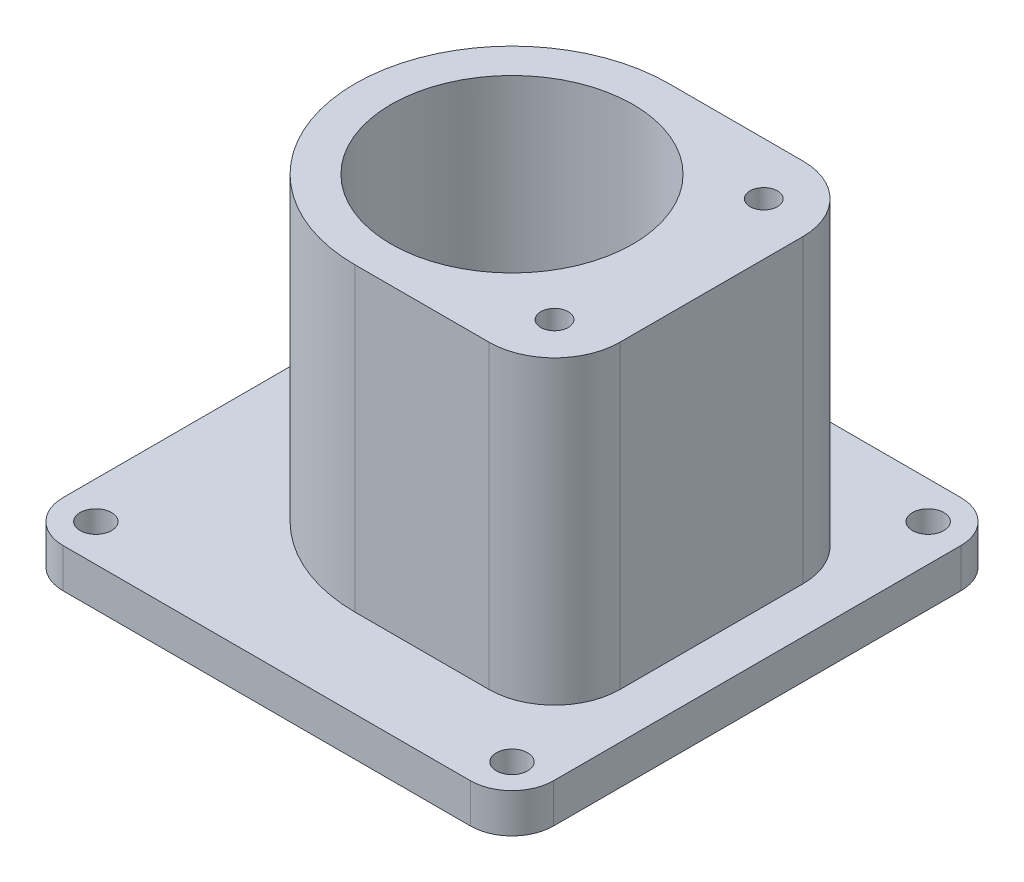
SolidWorks part; units mm, degrees
note: '?' marks a value the reader was unsure of.
ref_plane "Front Plane" through (0, 0, 0) normal (0, 0, 1) x (1, 0, 0)
ref_plane "Top Plane" through (0, 0, 0) normal (0, 1, 0) x (1, 0, 0)
ref_plane "Right Plane" through (0, 0, 0) normal (1, 0, 0) x (0, 0, -1)
ref_axis "X" through (88.99, 0, 0) along (-1, 0, 0)?
ref_axis "Y" through (0, 55, 0) along (0, -1, 0)?
ref_axis "Z" through (0, 0, -88.99) along (0, 0, 1)?
sketch "Sketch1" plane through (0, 0, 0) normal (0, 0, 1) x (1, 0, 0)
  line L0 (0, 0) -> (0, 52.8087) construction
  line L1 (-16.5, 0) -> (-34, 0)
  line L2 (-34, 0) -> (-34, 6)
  line L3 (-34, 6) -> (-24, 6)
  line L4 (-24, 6) -> (-24, 25)
  line L14 (-24, 25) -> (-18.5, 25)
  line L15 (-18.5, 25) -> (-18.5, 13)
  line L21 (-18.5, 13) -> (-16.5, 13)
  line L24 (-16.5, 13) -> (-16.5, 0)
  point P3 (0, 0)
  point P9 (0, 0)
  dimension "D2" = 25
  dimension "D3" = 12
  dimension "D4" = 48
  dimension "D5" = 10
  dimension "D6" = 6
  dimension "D7" = 18.5
  dimension "D10" = 33
revolve "Revolve1" add sketch "Sketch1" angle 360 about L0
sketch "Sketch2" plane through (0, 6, 0) normal (0, 1, 0) x (1, 0, 0)
  line L1 (37.5, -37.5) -> (-37.5, -37.5)
  line L2 (37.5, -37.5) -> (37.5, 37.5)
  line L3 (37.5, 37.5) -> (-37.5, 37.5)
  line L4 (-37.5, -37.5) -> (-37.5, 37.5)
  line L5 (37.5, -37.5) -> (-37.5, 37.5) construction
  line L6 (37.5, 37.5) -> (-37.5, -37.5) construction
  circle A0 centre (0, 0) radius 21
  point P0 (0, 0)
  point P7 (-3.2396, 8.1426)
  dimension "D1" = 75
extrude "Boss-Extrude1" add sketch "Sketch2" against normal up to surface (6 mm away) up to face at (0, 0, -16.5)
hole_wizard "M4 Clearance Hole1" positions "Sketch3" profile "Sketch4" hole size "M4" standard "DIN" end condition up to next
sketch "Sketch3" plane through (0, 0, 0) normal (0, -1, 0) x (-1, 0, 0)
  line L2 (31.8198, -31.8198) -> (-31.8198, -31.8198)
  line L3 (31.8198, -31.8198) -> (31.8198, 31.8198)
  line L4 (31.8198, 31.8198) -> (-31.8198, 31.8198)
  line L5 (-31.8198, -31.8198) -> (-31.8198, 31.8198)
  line L6 (31.8198, -31.8198) -> (-31.8198, 31.8198) construction
  line L7 (31.8198, 31.8198) -> (-31.8198, -31.8198) construction
  point P16 (0, 0)
  point P61 (-31.8198, 31.8198)
  point P64 (31.8198, 31.8198)
  point P67 (31.8198, -31.8198)
  point P70 (-31.8198, -31.8198)
  dimension "D1" = 90
sketch "Sketch4" plane through (0, 0, 0) normal (1, 0, 0) x (0, 0, -1)
  line L0 (0, 0) -> (0, 25)
  line L1 (0, 25) -> (2.4, 25)
  line L2 (2.4, 25) -> (2.4, 0)
  line L5 (2.4, 0) -> (0, 0)
  line L11 (0, -6.35) -> (0, 107.95) construction
  dimension "Thru Hole Dia." = 4.8
  dimension "Thru Hole Depth" = 25
fillet "Fillet1" radius 6.35 4 edges at (37.5, 3, 37.5) (-37.5, 3, 37.5) (37.5, 3, -37.5) (-37.5, 3, -37.5)
sketch "Sketch5" plane through (0, 25, 0) normal (0, 1, 0) x (1, 0, 0)
  line L0 (0, 0) -> (6.5, 0) construction
  line L1 (0, 24) -> (6.5, 24)
  line L2 (0, -24) -> (6.5, -24)
  line L3 (6.5, 24) -> (30.5, 24)
  line L4 (30.5, 24) -> (30.5, -24)
  line L5 (30.5, -24) -> (6.5, -24)
  arc A0 (0, 24) -> (0, -24) centre (0, 0) ccw
  circle A2 centre (0, 0) radius 24 construction
  circle A3 centre (0, 0) radius 24 construction
  circle A5 centre (0, 0) radius 22.8091
  point P3 (5, 0)
  dimension "D1" = 6.5
extrude "Boss-Extrude2" add sketch "Sketch5" against normal up to surface (19 mm away) up to face at (31.8198, 6, -34.2198)
fillet "Fillet2" radius 10 2 edges at (30.5, 15.5, 24) (30.5, 15.5, -24)
hole_wizard "Ø3.0mm Dowel Hole1" [suppressed] positions "Sketch8" profile "Sketch7" hole size "Ø3.0" standard "DIN"
sketch "Sketch8" plane through (0, 25, 0) normal (0, 1, 0) x (1, 0, 0)
  line L0 (20.5, 24) -> (0, 24) construction
  line L2 (30.5, -14) -> (30.5, 14) construction
  point P0 (24.5, 9)
  point P2 (24.5, -9)
  dimension "D1" = 15
  dimension "D2" = 6
  dimension "D3" = 18
sketch "Sketch7" plane through (24.5, 25, -9) normal (1, 0, 0) x (0, 0, 1)
  line L0 (0, 0) -> (0, 6.9013)
  line L1 (0, 6.9013) -> (1.5, 6)
  line L2 (1.5, 6) -> (1.5, 0)
  line L5 (1.5, 0) -> (0, 0)
  line L10 (0, 6.9013) -> (-1.5, 6) construction
  line L11 (0, -6.35) -> (0, 107.95) construction
  dimension "Hole Dia." = 3
  dimension "Hole Depth" = 6
  dimension "Drill Angle" = 118
hole_wizard "M5 Tapped Hole1" positions "Sketch9" profile "Sketch10" tap size "M5" standard "DIN"
sketch "Sketch9" plane through (0, 25, 0) normal (0, 1, 0) x (1, 0, 0)
  line L1 (30.5, -14) -> (30.5, 14) construction
  line L2 (20.5, 24) -> (0, 24) construction
  line L3 (0, -24) -> (20.5, -24) construction
  point P0 (22.5, 16)
  point P2 (22.5, -16)
  dimension "D1" = 8
  dimension "D2" = 8
  dimension "D3" = 8
sketch "Sketch10" plane through (22.5, 25, -16) normal (1, 0, 0) x (0, 0, 1)
  line L0 (0, 0) -> (0, 13.6618)
  line L1 (0, 13.6618) -> (2.1, 12.4)
  line L2 (2.1, 12.4) -> (2.1, 0)
  line L5 (2.1, 0) -> (0, 0)
  line L10 (0, 13.6618) -> (-2.1, 12.4) construction
  line L11 (0, -6.35) -> (0, 107.95) construction
  dimension "Tap Drill Dia." = 4.2
  dimension "Tap Drill Depth" = 12.4
  dimension "Drill Angle" = 118
cosmetic thread "Hole Thread1" parameters "D1"=10, "D2"=5
cosmetic thread "Hole Thread2" parameters "D1"=10, "D2"=5
sketch "Sketch11" plane through (0, 25, 0) normal (0, 1, 0) x (1, 0, 0)
  line L3 (0, -24) -> (20.5, -24)
  line L4 (30.5, -14) -> (30.5, 14)
  line L5 (20.5, 24) -> (0, 24)
  line L6 (0, -24) -> (20.5, -24)
  line L7 (30.5, -14) -> (30.5, 14)
  line L8 (20.5, 24) -> (0, 24)
  circle A0 centre (0, 0) radius 18.5 construction
  circle A1 centre (0, 0) radius 18.5
  circle A2 centre (22.5, -16) radius 2.1 construction
  arc A3 (20.5, -24) -> (30.5, -14) centre (20.5, -14) ccw
  arc A4 (30.5, 14) -> (20.5, 24) centre (20.5, 14) ccw
  arc A5 (0, 24) -> (0, -24) centre (0, 0) ccw
  arc A6 (20.5, -24) -> (30.5, -14) centre (20.5, -14) ccw
  arc A7 (30.5, 14) -> (20.5, 24) centre (20.5, 14) ccw
  arc A8 (0, 24) -> (0, -24) centre (0, 0) ccw
  circle A9 centre (22.5, -16) radius 2.1
  circle A10 centre (22.5, 16) radius 2.1 construction
  circle A11 centre (22.5, 16) radius 2.1
  dimension "D1" = 0
extrude "Boss-Extrude3" add sketch "Sketch11" along normal blind 27
